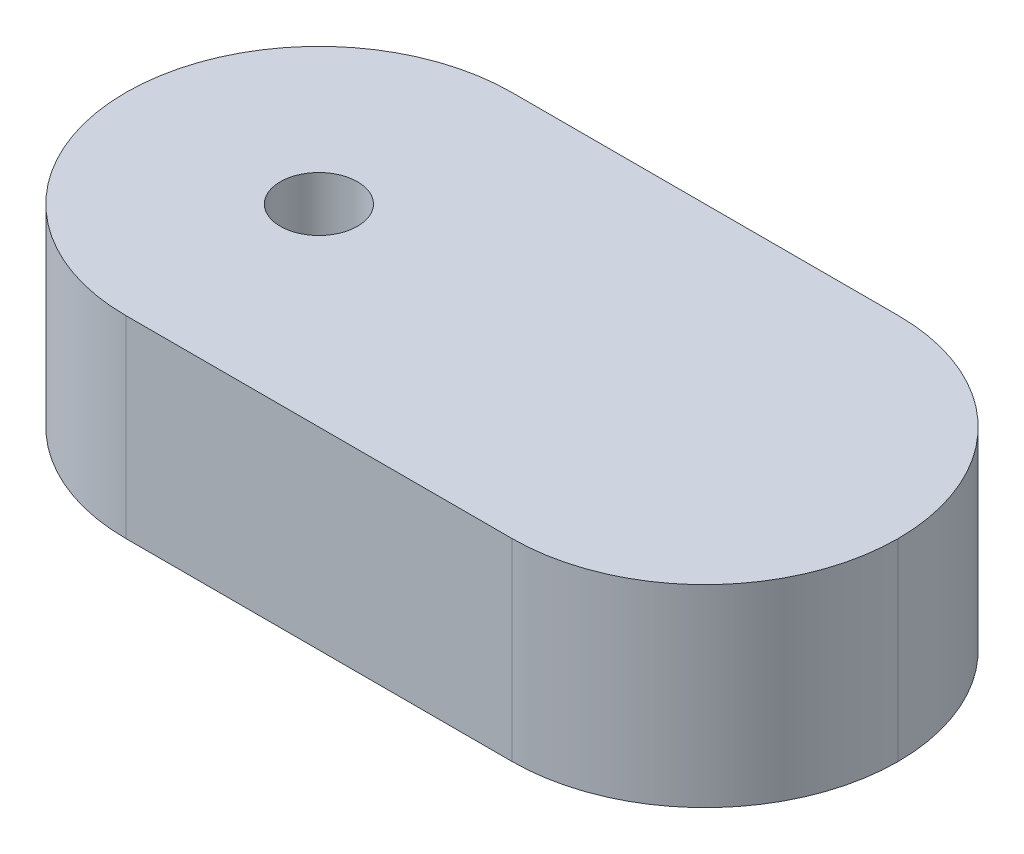
SolidWorks part; units mm, degrees
ref_plane "Plano frontal" through (0, 0, 0) normal (0, 0, 1) x (1, 0, 0)
ref_plane "Plano superior" through (0, 0, 0) normal (0, 1, 0) x (1, 0, 0)
ref_plane "Plano direito" through (0, 0, 0) normal (1, 0, 0) x (0, 0, -1)
sketch "Esboço2" plane through (0, 0, 0) normal (0, 1, 0) x (1, 0, 0)
  line L1 (-100, -50) -> (100, -50)
  line L2 (-100, -50) -> (-100, 50)
  line L3 (-100, 50) -> (100, 50)
  line L4 (100, -50) -> (100, 50)
  line L5 (-100, -50) -> (100, 50) construction
  line L6 (-100, 50) -> (100, -50) construction
  point P0 (0, 0)
  dimension "D1" = 100
  dimension "D2" = 200
extrude "Ressalto-extrusão1" add sketch "Esboço2" along normal blind 50
fillet "Filete1" radius 50 4 edges at (100, 25, -50) (100, 25, 50) (-100, 25, -50) (-100, 25, 50)
sketch "Esboço3" plane through (0, 0, 0) normal (0, -1, 0) x (1, 0, 0)
  circle A1 centre (50, 0) radius 15
  dimension "D1" = 30
extrude "Corte-extrusão1" cut sketch "Esboço3" against normal blind 25
sketch "Esboço4" plane through (0, 0, 0) normal (0, -1, 0) x (1, 0, 0)
  circle A0 centre (-50, 0) radius 10
  dimension "D1" = 20
extrude "Corte-extrusão2" cut sketch "Esboço4" against normal through all
